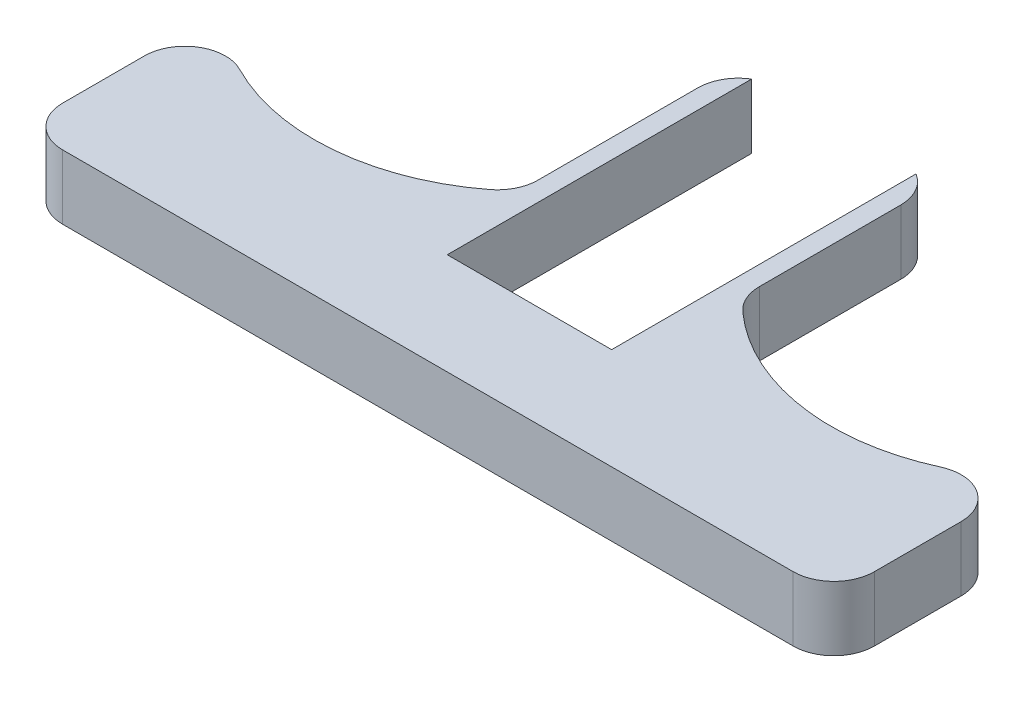
SolidWorks part; units mm, degrees
ref_plane "Front Plane" through (0, 0, 0) normal (0, 0, 1) x (1, 0, 0)
ref_plane "Top Plane" through (0, 0, 0) normal (0, 1, 0) x (1, 0, 0)
ref_plane "Right Plane" through (0, 0, 0) normal (1, 0, 0) x (0, 0, -1)
sketch "Sketch2" plane through (0, 0, 0) normal (0, 1, 0) x (1, 0, 0)
  line L0 (20, 0) -> (20, 20) construction
  line L1 (0, 0) -> (40, 0)
  line L2 (0, 0) -> (0, 10)
  line L4 (40, 0) -> (40, 10)
  line L5 (0, 0) -> (40, 10) construction
  line L6 (0, 10) -> (40, 0) construction
  line L7 (15, 9.4994) -> (15, 20.0021)
  line L9 (25, 20.0021) -> (25, 10.5006)
  line L10 (15, 20.0021) -> (15.95, 20.0021)
  line L12 (15.95, 20.0021) -> (15.95, 5.0021)
  line L13 (15.95, 5.0021) -> (24.05, 5.0021)
  line L14 (24.05, 20.0021) -> (24.05, 5.0021)
  line L15 (15.95, 20.0021) -> (24.05, 5.0021) construction
  line L16 (15.95, 5.0021) -> (24.05, 20.0021) construction
  line L17 (25, 20.0021) -> (24.05, 20.0021)
  arc A0 (15, 9.4994) -> (0, 10) centre (7.75, 17.2414) cw
  arc A1 (40, 10) -> (25, 10.5006) centre (32.75, 17.7419) cw
  point P4 (20, 5)
  point P18 (20, 12.5021)
  dimension "D5" = 10.6066
  dimension "D1" = 10
  dimension "D2" = 40
  dimension "D3" = 20
  dimension "D4" = 10
  dimension "D6" = 8.1
  dimension "D7" = 0.95
extrude "Boss-Extrude1" add sketch "Sketch2" along normal blind 3.175
fillet "Fillet1" radius 2 2 edges at (15, 1.5875, -9.4994) (25, 1.5875, -10.5006)
fillet "Fillet2" radius 2 4 edges at (25, 1.5875, -20.0021) (15, 1.5875, -20.0021) (0, 1.5875, -10) (40, 1.5875, -10)
fillet "Fillet3" radius 2 2 edges at (0, 1.5875, 0) (40, 1.5875, 0)
